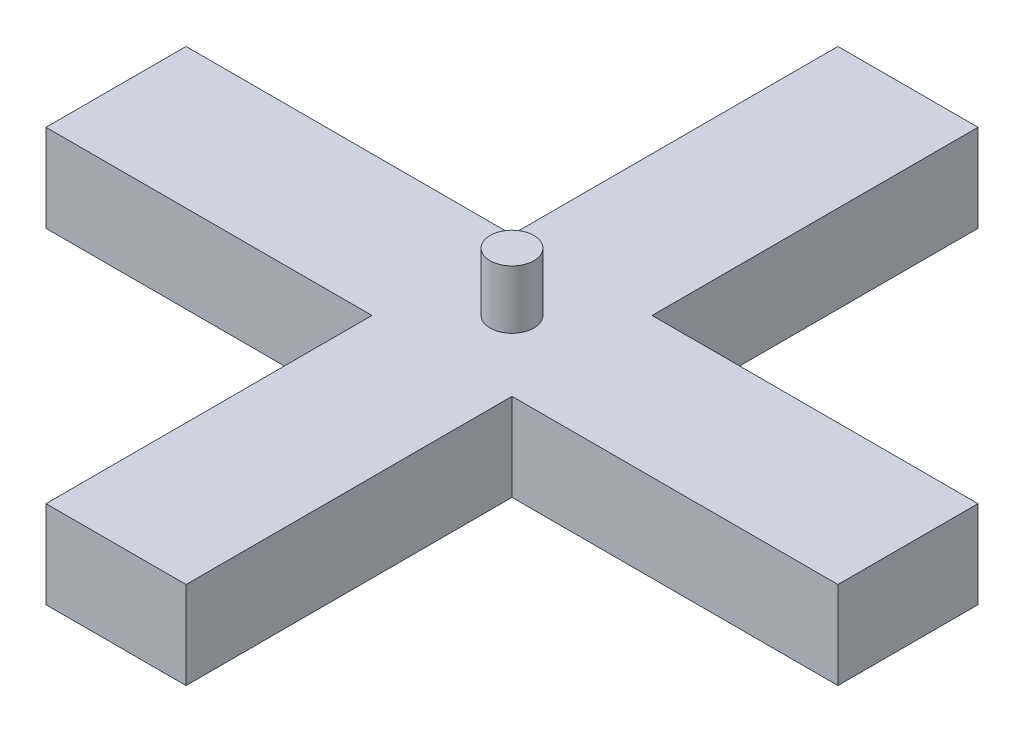
SolidWorks part; units mm, degrees
ref_plane "Front Plane" through (0, 0, 0) normal (0, 0, 1) x (1, 0, 0)
ref_plane "Top Plane" through (0, 0, 0) normal (0, 1, 0) x (1, 0, 0)
ref_plane "Right Plane" through (0, 0, 0) normal (1, 0, 0) x (0, 0, -1)
sketch "Sketch1" plane through (0, 0, 0) normal (0, 1, 0) x (1, 0, 0)
  line L0 (-4.8056, 8.0503) -> (-4.8056, -5.5197)
  line L1 (-4.8056, -5.5197) -> (-0.0056, -5.5197)
  line L3 (-4.8056, 8.0503) -> (-0.0056, 8.0503)
  line L4 (-4.8056, 8.0503) -> (-4.8056, -19.0897)
  line L5 (-4.8056, -19.0897) -> (-0.0056, -19.0897)
  line L6 (-0.0056, 8.0503) -> (-0.0056, -19.0897)
  line L7 (11.1644, -3.1197) -> (-15.9756, -3.1197)
  line L8 (11.1644, -3.1197) -> (11.1644, -7.9197)
  line L9 (11.1644, -7.9197) -> (-15.9756, -7.9197)
  line L10 (-15.9756, -3.1197) -> (-15.9756, -7.9197)
  line L11 (-0.0056, -19.0897) -> (-0.0056, 8.0503)
  line L12 (-0.0056, -19.0897) -> (-4.8056, -19.0897)
  line L13 (-4.8056, -19.0897) -> (-4.8056, 8.0503)
  line L14 (-0.0056, 8.0503) -> (-4.8056, 8.0503)
  line L15 (-15.9756, -7.9197) -> (11.1644, -7.9197)
  line L16 (-15.9756, -7.9197) -> (-15.9756, -3.1197)
  line L17 (-15.9756, -3.1197) -> (11.1644, -3.1197)
  line L18 (11.1644, -7.9197) -> (11.1644, -3.1197)
  circle A0 centre (-2.4056, -5.5197) radius 0.75
  point P23 (-2.4056, -5.5197)
  dimension "D3" = 1.5
  dimension "D1" = 27.14
  dimension "D2" = 4.8
  dimension "D4" = 4
extrude "Boss-Extrude1" add sketch "Sketch1" along normal blind 5 contours L1 A0 | L1 A0 region at (-2.4056, 0, 5.2014) region at (-2.4056, 0, 5.838)
extrude "Boss-Extrude2" add sketch "Sketch1<3>" along normal blind 3 contours L7 L10 L9 L4 | A0 L1 L6 L7 L4 | A0 L1 L4 L9 L6 | L9 L8 L7 L6 | L6 L9 L4 L5 | L7 L6 L3 L0 region at (-2.4056, 0, -2.4653) region at (-2.4056, 0, 4.2465) region at (-10.3906, 0, 5.5197) region at (-2.4056, 0, 6.793) region at (5.5794, 0, 5.5197) region at (-2.4056, 0, 13.5047)
sketch "Sketch1<3>" plane through (0, 0, 0) normal (0, 1, 0) x (1, 0, 0) same geometry as "Sketch1"
